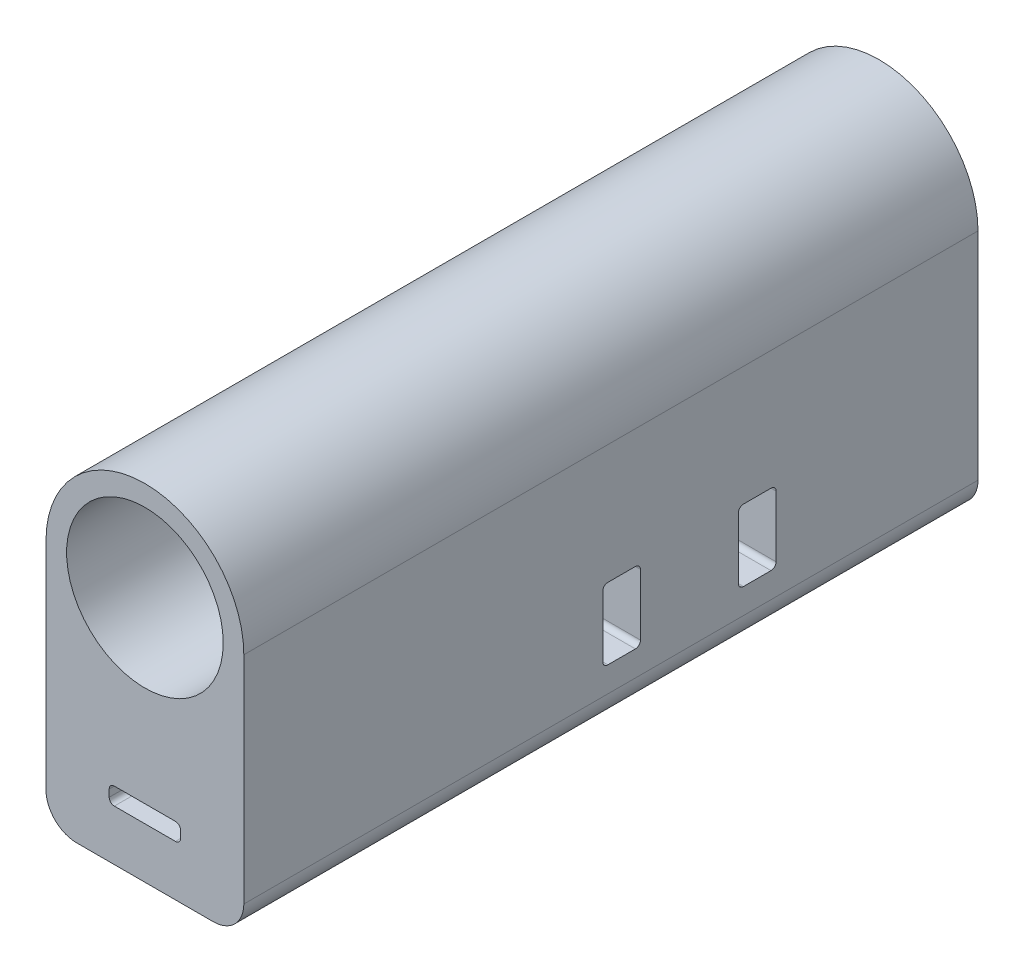
SolidWorks part; units mm, degrees
ref_plane "Front Plane" through (0, 0, 0) normal (0, 0, 1) x (1, 0, 0)
ref_plane "Top Plane" through (0, 0, 0) normal (0, 1, 0) x (1, 0, 0)
ref_plane "Right Plane" through (0, 0, 0) normal (1, 0, 0) x (0, 0, -1)
sketch "Sketch1" plane through (0, 0, 0) normal (0, 0, 1) x (1, 0, 0)
  line L24 (9.7, 0) -> (9.7, -21.17)
  line L45 (3.5, -18) -> (3.5, -18.7)
  line L46 (3, -17.5) -> (-3, -17.5)
  line L47 (-3.5, -18) -> (-3.5, -18.7)
  line L48 (3, -19.2) -> (-3, -19.2)
  line L54 (-9.7, 0) -> (-9.7, -21.17)
  line L55 (6.7, -24.17) -> (-6.7, -24.17)
  circle A1 centre (0, 0) radius 7.68
  arc A17 (9.7, 0) -> (-9.7, 0) centre (0, 0) ccw
  arc A43 (-3, -19.2) -> (-3.5, -18.7) centre (-3, -18.7) cw
  arc A44 (-3, -17.5) -> (-3.5, -18) centre (-3, -18) ccw
  arc A45 (3.5, -18.7) -> (3, -19.2) centre (3, -18.7) cw
  arc A46 (3, -17.5) -> (3.5, -18) centre (3, -18) cw
  arc A51 (9.7, -21.17) -> (6.7, -24.17) centre (6.7, -21.17) cw
  arc A52 (-9.7, -21.17) -> (-6.7, -24.17) centre (-6.7, -21.17) ccw
extrude "Boss-Extrude1" add sketch "Sketch1" along normal blind 72
sketch "Sketch2" plane through (0, 0, 0) normal (0, 0, 1) x (1, 0, 0)
  line L0 (-3.51, -9.93) -> (3.51, -9.93)
  line L1 (-5.66, -12.08) -> (-5.66, -19.21)
  line L2 (-3.51, -21.36) -> (3.51, -21.36)
  line L3 (5.66, -12.08) -> (5.66, -19.21)
  line L8 (3.5, -18) -> (3.5, -18.7)
  line L9 (3, -17.5) -> (-3, -17.5)
  line L10 (-3.5, -18) -> (-3.5, -18.7)
  line L11 (3, -19.2) -> (-3, -19.2)
  arc A0 (3.51, -21.36) -> (5.66, -19.21) centre (3.51, -19.21) ccw
  arc A1 (-5.66, -19.21) -> (-3.51, -21.36) centre (-3.51, -19.21) ccw
  arc A2 (3.51, -9.93) -> (5.66, -12.08) centre (3.51, -12.08) cw
  arc A3 (-3.51, -9.93) -> (-5.66, -12.08) centre (-3.51, -12.08) ccw
  circle A4 centre (0, -13.79) radius 1.7
  arc A9 (-3, -19.2) -> (-3.5, -18.7) centre (-3, -18.7) cw
  arc A10 (-3, -17.5) -> (-3.5, -18) centre (-3, -18) ccw
  arc A11 (3.5, -18.7) -> (3, -19.2) centre (3, -18.7) cw
  arc A12 (3, -17.5) -> (3.5, -18) centre (3, -18) cw
sketch "Sketch3" plane through (9.7, 0, 0) normal (1, 0, 0) x (0, 0, -1)
  line L26 (-36.3, -11.7) -> (-33.6, -11.7)
  line L27 (-36.8, -12.2) -> (-36.8, -18.2)
  line L28 (-36.3, -18.7) -> (-33.6, -18.7)
  line L29 (-33.1, -12.2) -> (-33.1, -18.2)
  line L36 (-23.0016, -11.7) -> (-20.3016, -11.7)
  line L37 (-23.5016, -12.2) -> (-23.5016, -18.2)
  line L38 (-23.0016, -18.7) -> (-20.3016, -18.7)
  line L39 (-19.8016, -12.2) -> (-19.8016, -18.2)
  arc A24 (-20.3016, -11.7) -> (-19.8016, -12.2) centre (-20.3016, -12.2) cw
  arc A25 (-20.3016, -18.7) -> (-19.8016, -18.2) centre (-20.3016, -18.2) ccw
  arc A26 (-23.5016, -18.2) -> (-23.0016, -18.7) centre (-23.0016, -18.2) ccw
  arc A27 (-23.0016, -11.7) -> (-23.5016, -12.2) centre (-23.0016, -12.2) ccw
  arc A28 (-33.6, -11.7) -> (-33.1, -12.2) centre (-33.6, -12.2) cw
  arc A29 (-33.6, -18.7) -> (-33.1, -18.2) centre (-33.6, -18.2) ccw
  arc A30 (-36.8, -18.2) -> (-36.3, -18.7) centre (-36.3, -18.2) ccw
  arc A31 (-36.3, -11.7) -> (-36.8, -12.2) centre (-36.3, -12.2) ccw
extrude "Cut-Extrude1" cut sketch "Sketch3" against normal up to surface (19.4 mm away) up to face at (-9.7, -10.585, 36)
